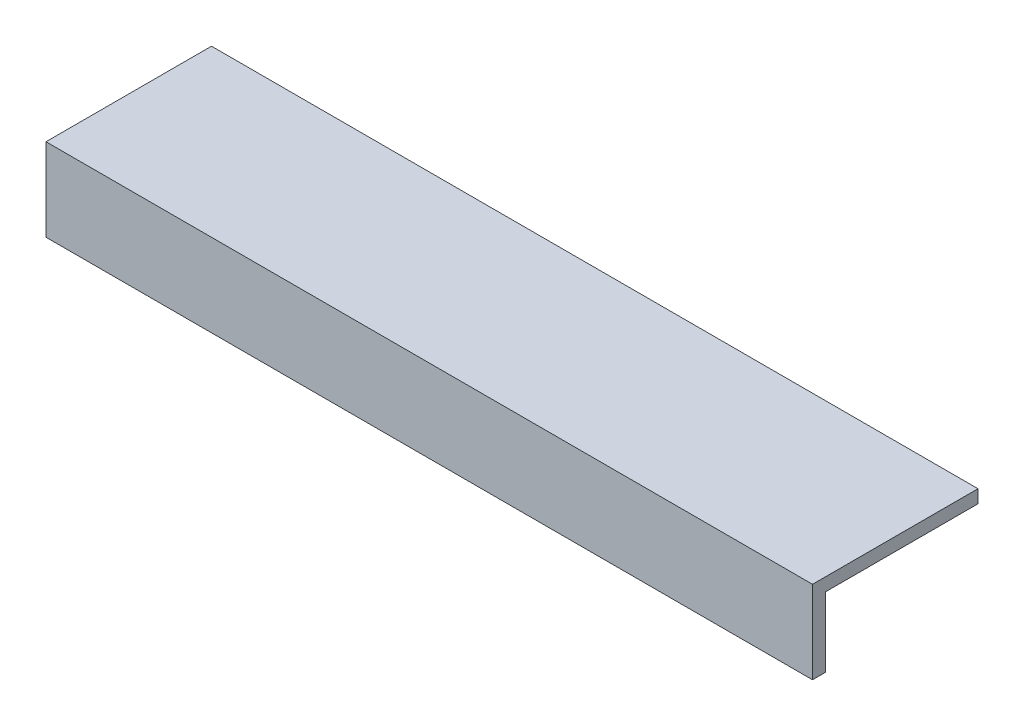
SolidWorks part; units mm, degrees
ref_plane "Alzado" through (0, 0, 0) normal (0, 0, 1) x (1, 0, 0)
ref_plane "Planta" through (0, 0, 0) normal (0, 1, 0) x (1, 0, 0)
ref_plane "Vista lateral" through (0, 0, 0) normal (1, 0, 0) x (0, 0, -1)
sketch "Croquis1" plane through (0, 0, 0) normal (1, 0, 0) x (0, 0, -1)
  line L0 (0, 0) -> (0, -38)
  line L1 (0, 0) -> (38, 0)
  line L2 (3, -3) -> (38, -3)
  line L3 (3, -3) -> (3, -38)
  line L4 (0, -38) -> (3, -38)
  line L5 (38, 0) -> (38, -3)
  dimension "D1" = 38
  dimension "D2" = 3
extrude "Saliente-Extruir1" add sketch "Croquis1" along normal blind 176
sketch "Croquis2" plane through (0, 0, 0) normal (0, 0, 1) x (1, 0, 0)
  line L0 (0, -19) -> (176, -19)
  line L1 (0, 0) -> (0, -38) construction
  line L2 (176, 0) -> (176, -38) construction
  line L3 (0, -19) -> (0, -38)
  line L4 (0, -38) -> (176, -38)
  line L5 (176, -38) -> (176, -19)
extrude "Cortar-Extruir1" cut sketch "Croquis2" against normal up to surface (3 mm away) up to face at (88, -20.5, -3)
